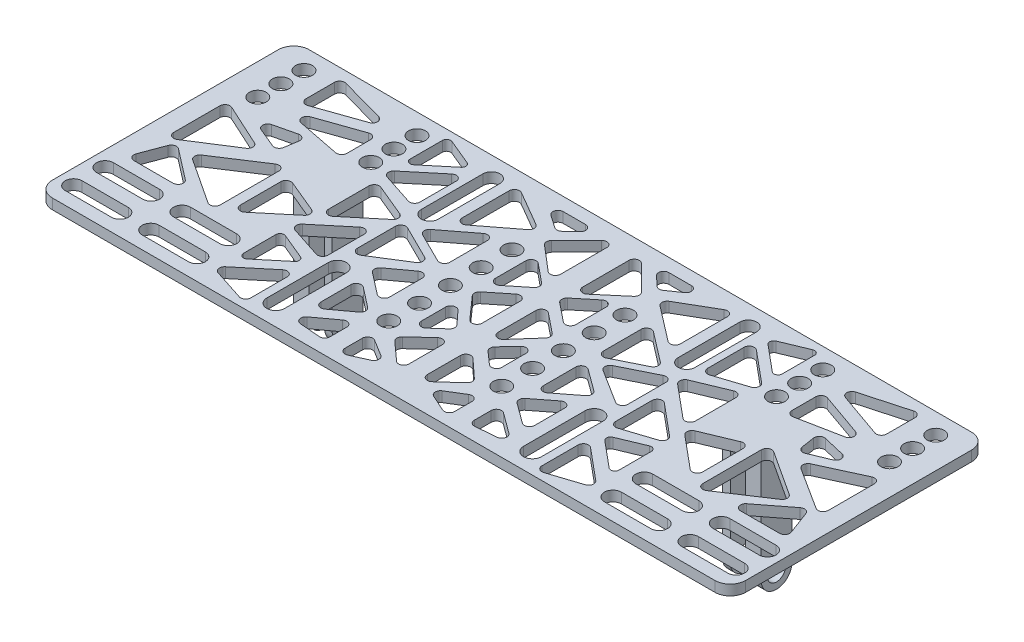
SolidWorks part; units mm, degrees
ref_plane "前视基准面" through (0, 0, 0) normal (0, 0, 1) x (1, 0, 0)
ref_plane "上视基准面" through (0, 0, 0) normal (0, 1, 0) x (1, 0, 0)
ref_plane "右视基准面" through (0, 0, 0) normal (1, 0, 0) x (0, 0, -1)
sketch "草图1" plane through (0, 0, 0) normal (0, 1, 0) x (1, 0, 0)
  line L1 (-67.5, -25) -> (67.5, -25)
  line L2 (-67.5, -25) -> (-67.5, 25)
  line L3 (-67.5, 25) -> (67.5, 25)
  line L4 (67.5, -25) -> (67.5, 25)
  line L5 (-67.5, -25) -> (67.5, 25) construction
  line L6 (-67.5, 25) -> (67.5, -25) construction
  point P0 (0, 0)
  dimension "D1" = 135
  dimension "D2" = 50
extrude "凸台-拉伸1" add sketch "草图1" along normal blind 2
sketch "草图2" plane through (0, 2, 0) normal (0, 1, 0) x (1, 0, 0)
  line L0 (-64.5, -20.85) -> (-55.5, -20.85) construction
  line L1 (-64.5, -19.2) -> (-55.5, -19.2)
  line L2 (-64.5, -22.5) -> (-55.5, -22.5)
  line L3 (-67.5, 25) -> (-67.5, -25) construction
  line L4 (-67.5, -25) -> (67.5, -25) construction
  line L5 (0, 25) -> (0, -25) construction
  line L6 (67.5, 25) -> (-67.5, 25) construction
  line L7 (-64.5, -14.75) -> (-55.5, -14.75) construction
  line L8 (-64.5, -13.1) -> (-55.5, -13.1)
  line L9 (-64.5, -16.4) -> (-55.5, -16.4)
  line L10 (-40.5, -20.85) -> (-49.5, -20.85) construction
  line L11 (-40.5, -19.2) -> (-49.5, -19.2)
  line L12 (-40.5, -22.5) -> (-49.5, -22.5)
  line L13 (-40.5, -14.75) -> (-49.5, -14.75) construction
  line L14 (-40.5, -13.1) -> (-49.5, -13.1)
  line L15 (-40.5, -16.4) -> (-49.5, -16.4)
  line L16 (-52.5, -25) -> (-52.5, -7.7597) construction
  line L17 (64.5, -20.85) -> (55.5, -20.85) construction
  line L18 (64.5, -19.2) -> (55.5, -19.2)
  line L19 (64.5, -22.5) -> (55.5, -22.5)
  line L20 (64.5, -14.75) -> (55.5, -14.75) construction
  line L21 (64.5, -13.1) -> (55.5, -13.1)
  line L22 (64.5, -16.4) -> (55.5, -16.4)
  line L23 (40.5, -20.85) -> (49.5, -20.85) construction
  line L24 (40.5, -19.2) -> (49.5, -19.2)
  line L25 (40.5, -22.5) -> (49.5, -22.5)
  line L26 (40.5, -14.75) -> (49.5, -14.75) construction
  line L27 (40.5, -13.1) -> (49.5, -13.1)
  line L28 (40.5, -16.4) -> (49.5, -16.4)
  arc A0 (-64.5, -19.2) -> (-64.5, -22.5) centre (-64.5, -20.85) ccw
  arc A1 (-55.5, -22.5) -> (-55.5, -19.2) centre (-55.5, -20.85) ccw
  arc A2 (-64.5, -13.1) -> (-64.5, -16.4) centre (-64.5, -14.75) ccw
  arc A3 (-55.5, -16.4) -> (-55.5, -13.1) centre (-55.5, -14.75) ccw
  arc A4 (-40.5, -19.2) -> (-40.5, -22.5) centre (-40.5, -20.85) cw
  arc A5 (-49.5, -22.5) -> (-49.5, -19.2) centre (-49.5, -20.85) cw
  arc A6 (-40.5, -13.1) -> (-40.5, -16.4) centre (-40.5, -14.75) cw
  arc A7 (-49.5, -16.4) -> (-49.5, -13.1) centre (-49.5, -14.75) cw
  arc A8 (64.5, -19.2) -> (64.5, -22.5) centre (64.5, -20.85) cw
  arc A9 (55.5, -22.5) -> (55.5, -19.2) centre (55.5, -20.85) cw
  arc A10 (64.5, -13.1) -> (64.5, -16.4) centre (64.5, -14.75) cw
  arc A11 (55.5, -16.4) -> (55.5, -13.1) centre (55.5, -14.75) cw
  arc A12 (40.5, -19.2) -> (40.5, -22.5) centre (40.5, -20.85) ccw
  arc A13 (49.5, -22.5) -> (49.5, -19.2) centre (49.5, -20.85) ccw
  arc A14 (40.5, -13.1) -> (40.5, -16.4) centre (40.5, -14.75) ccw
  arc A15 (49.5, -16.4) -> (49.5, -13.1) centre (49.5, -14.75) ccw
  point P2 (-60, -20.85)
  point P19 (-60, -14.75)
  point P24 (-45, -20.85)
  point P31 (-45, -14.75)
  point P40 (60, -20.85)
  point P47 (60, -14.75)
  point P54 (45, -20.85)
  point P61 (45, -14.75)
  dimension "D1" = 1.65
  dimension "D2" = 3
  dimension "D3" = 2.5
  dimension "D4" = 9
  dimension "D6" = 15
  dimension "D5" = 2
extrude "切除-拉伸1" cut sketch "草图2" against normal through all
sketch "草图3" plane through (0, 2, 0) normal (0, 1, 0) x (1, 0, 0)
  line L0 (-25, 21) -> (-25, 9) construction
  line L1 (-23.35, 21) -> (-23.35, 9)
  line L2 (-26.65, 21) -> (-26.65, 9)
  line L3 (0, 25) -> (0, -25) construction
  line L4 (67.5, 25) -> (-67.5, 25) construction
  line L5 (-67.5, -25) -> (67.5, -25) construction
  line L6 (25, 21) -> (25, 9) construction
  line L7 (23.35, 21) -> (23.35, 9)
  line L8 (26.65, 21) -> (26.65, 9)
  line L9 (-25, 15) -> (25, 15) construction
  line L10 (-25, -9) -> (-25, -21) construction
  line L11 (-23.25, -9) -> (-23.25, -21)
  line L12 (-26.75, -9) -> (-26.75, -21)
  line L13 (25, -9) -> (25, -21) construction
  line L14 (23.25, -9) -> (23.25, -21)
  line L15 (26.75, -9) -> (26.75, -21)
  line L16 (-25, -15) -> (25, -15) construction
  arc A0 (-23.35, 21) -> (-26.65, 21) centre (-25, 21) ccw
  arc A1 (-26.65, 9) -> (-23.35, 9) centre (-25, 9) ccw
  arc A2 (23.35, 21) -> (26.65, 21) centre (25, 21) cw
  arc A3 (26.65, 9) -> (23.35, 9) centre (25, 9) cw
  arc A4 (-23.25, -9) -> (-26.75, -9) centre (-25, -9) ccw
  arc A5 (-26.75, -21) -> (-23.25, -21) centre (-25, -21) ccw
  arc A6 (23.25, -9) -> (26.75, -9) centre (25, -9) cw
  arc A7 (26.75, -21) -> (23.25, -21) centre (25, -21) cw
  point P2 (-25, 15)
  point P15 (25, 15)
  point P24 (-25, -15)
  point P31 (25, -15)
  dimension "D4" = 1.75
  dimension "D5" = 1.65
  dimension "D1" = 50
  dimension "D2" = 4
  dimension "D3" = 12
  dimension "D6" = 4
  dimension "D7" = 12
extrude "切除-拉伸2" cut sketch "草图3" against normal through all
sketch "草图4" plane through (0, 2, 0) normal (0, 1, 0) x (1, 0, 0)
  line L0 (0, 25) -> (0, -25) construction
  line L1 (67.5, 25) -> (-67.5, 25) construction
  line L2 (-67.5, -25) -> (67.5, -25) construction
  circle A0 centre (-11, 11) radius 1.65
  circle A1 centre (11, 11) radius 1.65
  circle A2 centre (-11, 5) radius 1.65
  circle A3 centre (11, 5) radius 1.65
  circle A4 centre (-11, -1) radius 1.65
  circle A5 centre (11, -1) radius 1.65
  circle A6 centre (-11, -7) radius 1.65
  circle A7 centre (11, -7) radius 1.65
  circle A8 centre (-11, -13) radius 1.65
  circle A9 centre (11, -13) radius 1.65
  dimension "D1" = 3.3
  dimension "D2" = 22
  dimension "D3" = 14
  dimension "D4" = 5
extrude "切除-拉伸3" cut sketch "草图4" against normal through all
sketch "草图5" plane through (0, 0, 0) normal (0, -1, 0) x (1, 0, 0)
  line L0 (67.5, -25) -> (-67.5, -25) construction
  line L1 (-39.5, -9) -> (-38, -9)
  line L2 (-39.5, -9) -> (-39.5, -3)
  line L3 (-39.5, -3) -> (-38, -3)
  line L4 (-38, -9) -> (-38, -3)
  line L5 (-39.5, -9) -> (-38, -3) construction
  line L6 (-39.5, -3) -> (-38, -9) construction
  line L7 (0, 25) -> (0, -25) construction
  line L8 (-67.5, 25) -> (67.5, 25) construction
  line L9 (45.5, -3) -> (42.5, -9) construction
  line L10 (-45.5, -9) -> (-42.5, -9)
  line L11 (-45.5, -9) -> (-45.5, -3)
  line L12 (-45.5, -3) -> (-42.5, -3)
  line L13 (-42.5, -9) -> (-42.5, -3)
  line L14 (-45.5, -9) -> (-42.5, -3) construction
  line L15 (-45.5, -3) -> (-42.5, -9) construction
  line L16 (45.5, -9) -> (42.5, -3) construction
  line L17 (39.5, -3) -> (38, -9) construction
  line L18 (39.5, -9) -> (38, -3) construction
  line L19 (42.5, -9) -> (42.5, -3)
  line L20 (45.5, -3) -> (42.5, -3)
  line L21 (45.5, -9) -> (45.5, -3)
  line L22 (45.5, -9) -> (42.5, -9)
  line L23 (38, -9) -> (38, -3)
  line L24 (39.5, -3) -> (38, -3)
  line L25 (39.5, -9) -> (39.5, -3)
  line L26 (39.5, -9) -> (38, -9)
  point P0 (-38.75, -6)
  point P12 (-44, -6)
  point P25 (44, -6)
  point P26 (38.75, -6)
  dimension "D1" = 16
  dimension "D2" = 1.5
  dimension "D3" = 3
  dimension "D4" = 3
  dimension "D5" = 79
  dimension "D6" = 6
extrude "凸台-拉伸2" add sketch "草图5" along normal blind 24.5
fillet "圆角1" radius 3 8 edges at (-44, -24.5, -3) (-44, -24.5, -9) (-38.75, -24.5, -9) (-38.75, -24.5, -3) (38.75, -24.5, -9) (38.75, -24.5, -3) (44, -24.5, -9) (44, -24.5, -3)
sketch "草图6" plane through (45.5, 0, 0) normal (1, 0, 0) x (0, 0, -1)
  circle A0 centre (6, -21.5) radius 1.75
  dimension "D1" = 3.5
fillet "圆角3" radius 3 4 edges at (67.5, 1, 25) (67.5, 1, -25) (-67.5, 1, 25) (-67.5, 1, -25)
sketch "草图12" plane through (0, 2, 0) normal (0, 1, 0) x (1, 0, 0)
  line L0 (-63.7341, 6.8317) -> (-63.7341, -2.1456)
  line L1 (-62.1953, -2.9881) -> (-54.0246, 2.237)
  line L2 (-54.146, 3.9882) -> (-62.3167, 7.7404)
  line L3 (-57.2351, -3.2541) -> (-48.5324, 2.4295)
  line L4 (-46.9856, 1.5922) -> (-46.9856, -9.824)
  line L5 (-48.5357, -10.6591) -> (-57.2384, -4.9265)
  line L6 (-60.5319, -4.412) -> (-54.6423, -8.9715)
  line L7 (-55.2545, -10.7622) -> (-62.8532, -10.7622)
  line L8 (-63.7895, -9.4112) -> (-62.0804, -4.8518)
  line L9 (-45.0046, -0.0137) -> (-45.0046, -7.8954)
  line L10 (-43.3646, -8.6637) -> (-37.0568, -3.4093)
  line L11 (-37.3124, -1.7178) -> (-43.6201, 0.9094)
  line L12 (-35.7606, 12.8448) -> (-29.6612, 17.9257)
  line L13 (-28.0212, 17.1574) -> (-28.0212, 10.0875)
  line L14 (-29.3312, 9.1368) -> (-35.4306, 11.1258)
  line L15 (-36.0706, -19.7607) -> (-29.9713, -14.6798)
  line L16 (-28.3312, -15.4482) -> (-28.3312, -22.5181)
  line L17 (-29.6413, -23.4688) -> (-35.7406, -21.4798)
  line L21 (-36.5606, -9.4112) -> (-36.5606, -15.7165)
  line L22 (-30.4068, -10.7745) -> (-35.453, -8.6727)
  line L23 (-35.2486, -16.3312) -> (-30.2024, -12.1277)
  line L24 (-34.9186, 15.7679) -> (-29.8724, 19.9714)
  line L25 (-36.2306, 22.6878) -> (-36.2306, 16.3825)
  line L26 (-30.0768, 21.3246) -> (-35.123, 23.4264)
  line L30 (-35.717, 7.8679) -> (-35.717, -0.0137)
  line L31 (-34.0769, -0.7821) -> (-27.7692, 4.4724)
  line L32 (-28.0247, 6.1638) -> (-34.3325, 8.791)
  line L33 (-55.6863, 6.8317) -> (-51.8666, 5.2407)
  line L34 (-50.4943, 6.0082) -> (-50.0866, 8.596)
  line L35 (-51.304, 9.7249) -> (-55.5314, 8.7281)
  line L36 (-35.7606, -5.0753) -> (-29.6612, 0.0056)
  line L37 (-28.0212, -0.7627) -> (-28.0212, -7.8326)
  line L38 (-29.3312, -8.7834) -> (-35.4306, -6.7943)
  line L39 (0, 25) -> (0, -25) construction
  line L40 (64.5, 25) -> (-64.5, 25) construction
  line L41 (-64.5, -25) -> (64.5, -25) construction
  arc A0 (-43.6201, 0.9094) -> (-45.0046, -0.0137) centre (-44.0046, -0.0137) ccw
  arc A1 (-45.0046, -7.8954) -> (-43.3646, -8.6637) centre (-44.0046, -7.8954) ccw
  arc A2 (-37.0568, -3.4093) -> (-37.3124, -1.7178) centre (-37.6969, -2.6409) ccw
  arc A3 (-28.0212, 10.0875) -> (-29.3312, 9.1368) centre (-29.0212, 10.0875) cw
  arc A4 (-29.6612, 17.9257) -> (-28.0212, 17.1574) centre (-29.0212, 17.1574) cw
  arc A5 (-35.4306, 11.1258) -> (-35.7606, 12.8448) centre (-35.1206, 12.0765) cw
  arc A6 (-28.3312, -22.5181) -> (-29.6413, -23.4688) centre (-29.3312, -22.5181) cw
  arc A7 (-29.9713, -14.6798) -> (-28.3312, -15.4482) centre (-29.3312, -15.4482) cw
  arc A8 (-35.7406, -21.4798) -> (-36.0706, -19.7607) centre (-35.4306, -20.5291) cw
  arc A12 (-35.453, -8.6727) -> (-36.5606, -9.4112) centre (-35.7606, -9.4112) ccw
  arc A13 (-30.2024, -12.1277) -> (-30.4068, -10.7745) centre (-30.7144, -11.513) ccw
  arc A14 (-36.5606, -15.7165) -> (-35.2486, -16.3312) centre (-35.7606, -15.7165) ccw
  arc A15 (-51.8666, 5.2407) -> (-50.4943, 6.0082) centre (-51.4821, 6.1638) ccw
  arc A16 (-50.0866, 8.596) -> (-51.304, 9.7249) centre (-51.0744, 8.7516) ccw
  arc A17 (-55.5314, 8.7281) -> (-55.6863, 6.8317) centre (-55.3019, 7.7548) ccw
  arc A18 (-27.7692, 4.4724) -> (-28.0247, 6.1638) centre (-28.4092, 5.2407) ccw
  arc A19 (-34.3325, 8.791) -> (-35.717, 7.8679) centre (-34.717, 7.8679) ccw
  arc A20 (-35.717, -0.0137) -> (-34.0769, -0.7821) centre (-34.717, -0.0137) ccw
  arc A21 (-29.6612, 0.0056) -> (-28.0212, -0.7627) centre (-29.0212, -0.7627) cw
  arc A22 (-28.0212, -7.8326) -> (-29.3312, -8.7834) centre (-29.0212, -7.8326) cw
  arc A23 (-35.4306, -6.7943) -> (-35.7606, -5.0753) centre (-35.1206, -5.8436) cw
  arc A24 (-48.5357, -10.6591) -> (-46.9856, -9.824) centre (-47.9856, -9.824) ccw
  arc A25 (-46.9856, 1.5922) -> (-48.5324, 2.4295) centre (-47.9856, 1.5922) ccw
  arc A26 (-57.2351, -3.2541) -> (-57.2384, -4.9265) centre (-56.6883, -4.0914) ccw
  arc A27 (-55.2545, -10.7622) -> (-54.6423, -8.9715) centre (-55.2545, -9.7622) ccw
  arc A28 (-62.8532, -10.7622) -> (-63.7895, -9.4112) centre (-62.8532, -9.7622) cw
  arc A29 (-62.0804, -4.8518) -> (-60.5319, -4.412) centre (-61.144, -5.2028) cw
  arc A30 (-54.146, 3.9882) -> (-54.0246, 2.237) centre (-54.5634, 3.0794) cw
  arc A31 (-62.1953, -2.9881) -> (-63.7341, -2.1456) centre (-62.7341, -2.1456) cw
  arc A32 (-63.7341, 6.8317) -> (-62.3167, 7.7404) centre (-62.7341, 6.8317) cw
  arc A33 (-36.2306, 16.3825) -> (-34.9186, 15.7679) centre (-35.4306, 16.3825) ccw
  arc A34 (-35.123, 23.4264) -> (-36.2306, 22.6878) centre (-35.4306, 22.6878) ccw
  arc A35 (-29.8724, 19.9714) -> (-30.0768, 21.3246) centre (-30.3844, 20.5861) ccw
extrude "切除-拉伸8" cut sketch "草图12" against normal through all
sketch "草图13" plane through (0, 2, 0) normal (0, 1, 0) x (1, 0, 0)
  line L0 (-26.3284, 3.6434) -> (-26.3284, -3.7782)
  line L1 (-24.7954, -4.6243) -> (-18.2042, -0.4723)
  line L2 (-18.2928, 1.2696) -> (-24.884, 4.5393)
  line L3 (-22.2153, 4.8144) -> (-16.4065, 1.9329)
  line L4 (-14.9622, 2.8287) -> (-14.9622, 10.1753)
  line L5 (-16.5716, 10.9681) -> (-22.3803, 6.503)
  line L6 (-19.634, 10.7521) -> (-12.8519, 15.9654)
  line L7 (-12.9589, 17.6229) -> (-19.741, 21.5638)
  line L8 (-21.2435, 20.6991) -> (-21.2435, 11.5449)
  line L9 (-20.7454, -4.8066) -> (-16.5546, -1.725)
  line L10 (-14.9622, -2.5307) -> (-14.9622, -8.8711)
  line L11 (-16.576, -9.6605) -> (-20.7669, -6.4017)
  line L12 (-19.2026, -9.7572) -> (-15.3324, -12.7666)
  line L13 (-15.3539, -14.3617) -> (-19.224, -17.2074)
  line L14 (-20.8164, -16.4017) -> (-20.8164, -10.5466)
  line L15 (-19.6599, -20.255) -> (-15.6493, -17.306)
  line L16 (-14.0569, -18.1117) -> (-14.0569, -21.3933)
  line L17 (-15.1396, -22.3899) -> (-19.1502, -22.0572)
  line L18 (-12.4686, 22.4368) -> (-8.1041, 22.4368)
  line L19 (-7.4241, 20.7035) -> (-9.2906, 18.9726)
  line L20 (-13.0382, 20.6148) -> (-10.5402, 18.8838)
  line L21 (-8.7288, 16.4582) -> (-3.8639, 21.3231)
  line L22 (-2.1568, 20.616) -> (-2.1568, 11.616)
  line L23 (-3.8045, 10.8541) -> (-8.6693, 14.9892)
  line L24 (-6.1824, 11.291) -> (-2.5396, 8.2965)
  line L25 (-2.5475, 6.7451) -> (-6.1903, 3.8124)
  line L26 (-7.8174, 4.5913) -> (-7.8174, 10.5185)
  line L27 (-7.0005, 0.8319) -> (-3.1746, 3.912)
  line L28 (-1.5475, 3.133) -> (-1.5475, -4.2616)
  line L29 (-3.2957, -4.925) -> (-7.1216, -0.6105)
  line L30 (-7.8174, -5.1154) -> (-7.8174, -9.8023)
  line L31 (-6.1539, -10.5505) -> (-3.776, -8.4419)
  line L32 (-3.7044, -7.0157) -> (-6.0823, -4.4374)
  line L33 (-7.0118, -14.3399) -> (-3.4637, -11.0675)
  line L34 (-1.7858, -11.8026) -> (-1.7858, -18.2781)
  line L35 (-3.4559, -19.0204) -> (-7.0039, -15.8172)
  line L36 (-10.6733, -18.4621) -> (-10.6733, -21.8412)
  line L37 (-9.2648, -22.754) -> (-6.0857, -21.3312)
  line L38 (-5.9701, -19.5668) -> (-9.1492, -17.6104)
  arc A0 (-7.4241, 20.7035) -> (-8.1041, 22.4368) centre (-8.1041, 21.4368) ccw
  arc A1 (-12.4686, 22.4368) -> (-13.0382, 20.6148) centre (-12.4686, 21.4368) ccw
  arc A2 (-10.5402, 18.8838) -> (-9.2906, 18.9726) centre (-9.9706, 19.7058) ccw
  arc A3 (-3.8045, 10.8541) -> (-2.1568, 11.616) centre (-3.1568, 11.616) ccw
  arc A4 (-2.1568, 20.616) -> (-3.8639, 21.3231) centre (-3.1568, 20.616) ccw
  arc A5 (-8.7288, 16.4582) -> (-8.6693, 14.9892) centre (-8.0216, 15.7511) ccw
  arc A6 (-2.5475, 6.7451) -> (-2.5396, 8.2965) centre (-3.1746, 7.5241) ccw
  arc A7 (-6.1824, 11.291) -> (-7.8174, 10.5185) centre (-6.8174, 10.5185) ccw
  arc A8 (-7.8174, 4.5913) -> (-6.1903, 3.8124) centre (-6.8174, 4.5913) ccw
  arc A9 (-1.5475, 3.133) -> (-3.1746, 3.912) centre (-2.5475, 3.133) ccw
  arc A10 (-7.0005, 0.8319) -> (-7.1216, -0.6105) centre (-6.3733, 0.0529) ccw
  arc A11 (-3.2957, -4.925) -> (-1.5475, -4.2616) centre (-2.5475, -4.2616) ccw
  arc A12 (-3.776, -8.4419) -> (-3.7044, -7.0157) centre (-4.4395, -7.6937) ccw
  arc A13 (-6.0823, -4.4374) -> (-7.8174, -5.1154) centre (-6.8174, -5.1154) ccw
  arc A14 (-7.8174, -9.8023) -> (-6.1539, -10.5505) centre (-6.8174, -9.8023) ccw
  arc A15 (-3.4559, -19.0204) -> (-1.7858, -18.2781) centre (-2.7858, -18.2781) ccw
  arc A16 (-1.7858, -11.8026) -> (-3.4637, -11.0675) centre (-2.7858, -11.8026) ccw
  arc A17 (-7.0118, -14.3399) -> (-7.0039, -15.8172) centre (-6.3338, -15.075) ccw
  arc A18 (-10.6733, -21.8412) -> (-9.2648, -22.754) centre (-9.6733, -21.8412) ccw
  arc A19 (-6.0857, -21.3312) -> (-5.9701, -19.5668) centre (-6.4942, -20.4184) ccw
  arc A20 (-9.1492, -17.6104) -> (-10.6733, -18.4621) centre (-9.6733, -18.4621) ccw
  arc A21 (-15.6493, -17.306) -> (-14.0569, -18.1117) centre (-15.0569, -18.1117) cw
  arc A22 (-14.0569, -21.3933) -> (-15.1396, -22.3899) centre (-15.0569, -21.3933) cw
  arc A23 (-19.1502, -22.0572) -> (-19.6599, -20.255) centre (-19.0675, -21.0606) cw
  arc A24 (-15.3324, -12.7666) -> (-15.3539, -14.3617) centre (-15.9463, -13.556) cw
  arc A25 (-19.224, -17.2074) -> (-20.8164, -16.4017) centre (-19.8164, -16.4017) cw
  arc A26 (-20.8164, -10.5466) -> (-19.2026, -9.7572) centre (-19.8164, -10.5466) cw
  arc A27 (-16.576, -9.6605) -> (-14.9622, -8.8711) centre (-15.9622, -8.8711) ccw
  arc A28 (-14.9622, -2.5307) -> (-16.5546, -1.725) centre (-15.9622, -2.5307) ccw
  arc A29 (-20.7454, -4.8066) -> (-20.7669, -6.4017) centre (-20.153, -5.6122) ccw
  arc A30 (-18.2928, 1.2696) -> (-18.2042, -0.4723) centre (-18.7372, 0.3738) cw
  arc A31 (-24.7954, -4.6243) -> (-26.3284, -3.7782) centre (-25.3284, -3.7782) cw
  arc A32 (-26.3284, 3.6434) -> (-24.884, 4.5393) centre (-25.3284, 3.6434) cw
  arc A33 (-16.5716, 10.9681) -> (-14.9622, 10.1753) centre (-15.9622, 10.1753) cw
  arc A34 (-14.9622, 2.8287) -> (-16.4065, 1.9329) centre (-15.9622, 2.8287) cw
  arc A35 (-22.2153, 4.8144) -> (-22.3803, 6.503) centre (-21.7709, 5.7102) cw
  arc A36 (-21.2435, 11.5449) -> (-19.634, 10.7521) centre (-20.2435, 11.5449) ccw
  arc A37 (-12.8519, 15.9654) -> (-12.9589, 17.6229) centre (-13.4613, 16.7582) ccw
  arc A38 (-19.741, 21.5638) -> (-21.2435, 20.6991) centre (-20.2435, 20.6991) ccw
  point P61 (-7.8174, 0.1742)
  point P118 (-21.2435, 22.4368)
  dimension "D1" = 1
extrude "切除-拉伸9" cut sketch "草图13" against normal through all
mirror "镜向1" about plane through (0, 0, 0) normal (1, 0, 0) of "切除-拉伸9", "切除-拉伸8"
extrude "切除-拉伸10" cut sketch "草图6" against normal through all
chamfer "倒角1" distance 1 angle 45 4 edges at (45.5, 0, -6) (38, 0, -6) (-38, 0, -6) (-45.5, 0, -6)
sketch "草图14" plane through (0, 2, 0) normal (0, 1, 0) x (1, 0, 0)
  line L0 (-61.5, 21) -> (-39.5, 21) construction
  line L1 (-67.5, 22) -> (-67.5, -22) construction
  line L2 (64.5, 25) -> (-64.5, 25) construction
  line L3 (0, 25) -> (0, -25) construction
  line L4 (-64.5, -25) -> (64.5, -25) construction
  circle A0 centre (-61.5, 21) radius 1.65
  circle A1 centre (-39.5, 21) radius 1.65
  circle A2 centre (39.5, 21) radius 1.65
  circle A3 centre (61.5, 21) radius 1.65
  circle A4 centre (-61.5, 16.5) radius 1.65
  circle A5 centre (-39.5, 16.5) radius 1.65
  circle A6 centre (39.5, 16.5) radius 1.65
  circle A7 centre (61.5, 16.5) radius 1.65
  circle A8 centre (-61.5, 12) radius 1.65
  circle A9 centre (-39.5, 12) radius 1.65
  circle A10 centre (39.5, 12) radius 1.65
  circle A11 centre (61.5, 12) radius 1.65
  dimension "D1" = 3.3
  dimension "D2" = 3.3
  dimension "D3" = 22
  dimension "D4" = 6
  dimension "D5" = 4
  dimension "D6" = 3
extrude "切除-拉伸11" cut sketch "草图14" against normal through all
sketch "草图15" plane through (0, 2, 0) normal (0, 1, 0) x (1, 0, 0)
  line L0 (-56.5342, 21.9586) -> (-56.5342, 16.4027)
  line L1 (-55.2031, 15.4591) -> (-46.3542, 18.5644)
  line L2 (-46.4184, 20.4718) -> (-55.2673, 22.9223)
  line L3 (-53.0889, 13.7967) -> (-44.6759, 16.7491)
  line L4 (-43.3447, 15.8055) -> (-43.3447, 11.187)
  line L5 (-44.539, 10.2061) -> (-52.9521, 11.8722)
  arc A0 (-44.539, 10.2061) -> (-43.3447, 11.187) centre (-44.3447, 11.187) ccw
  arc A1 (-43.3447, 15.8055) -> (-44.6759, 16.7491) centre (-44.3447, 15.8055) ccw
  arc A2 (-53.0889, 13.7967) -> (-52.9521, 11.8722) centre (-52.7578, 12.8532) ccw
  arc A3 (-56.5342, 16.4027) -> (-55.2031, 15.4591) centre (-55.5342, 16.4027) ccw
  arc A4 (-46.3542, 18.5644) -> (-46.4184, 20.4718) centre (-46.6853, 19.508) ccw
  arc A5 (-55.2673, 22.9223) -> (-56.5342, 21.9586) centre (-55.5342, 21.9586) ccw
  dimension "D1" = 1
extrude "切除-拉伸12" cut sketch "草图15" against normal through all
mirror "镜向2" about plane through (0, 0, 0) normal (1, 0, 0) of "切除-拉伸12", "切除-拉伸11"
